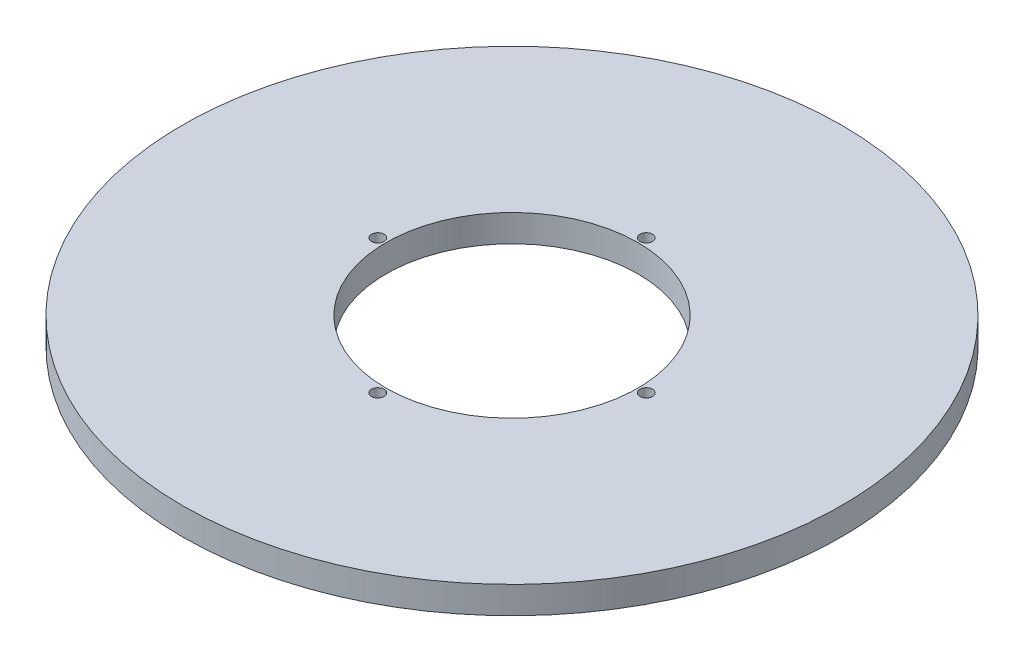
SolidWorks part; units mm, degrees
ref_plane "Front Plane" through (0, 0, 0) normal (0, 0, 1) x (1, 0, 0)
ref_plane "Top Plane" through (0, 0, 0) normal (0, 1, 0) x (1, 0, 0)
ref_plane "Right Plane" through (0, 0, 0) normal (1, 0, 0) x (0, 0, -1)
sketch "Sketch1" plane through (0, 0, 0) normal (0, 1, 0) x (1, 0, 0)
  circle A0 centre (0, 0) radius 85
  dimension "FLANGE_OD" = 170
extrude "Boss-Extrude1" add sketch "Sketch1" along normal blind 7
sketch "Sketch2" plane through (0, 0, 0) normal (0, 1, 0) x (1, 0, 0)
  circle A0 centre (0, 0) radius 32.5
  dimension "BORE_D" = 65
extrude "Cut-Extrude1" cut sketch "Sketch2" along normal through all
sketch "Sketch3" plane through (0, 7, 0) normal (0, 1, 0) x (1, 0, 0)
  circle A0 centre (0, 0) radius 34.6199 construction
  circle A1 centre (-34.6199, 0) radius 1.6257
  dimension "BOLT_D" = 3.2514
  dimension "BOLT_PCD" = 69.2398
extrude "Cut-Extrude2" cut sketch "Sketch3" against normal blind 6.8727
pattern_circular "CirPattern1" count 4 over 360 about axis through (0, 0, 0) along (0, 1, 0) of "Cut-Extrude2"
